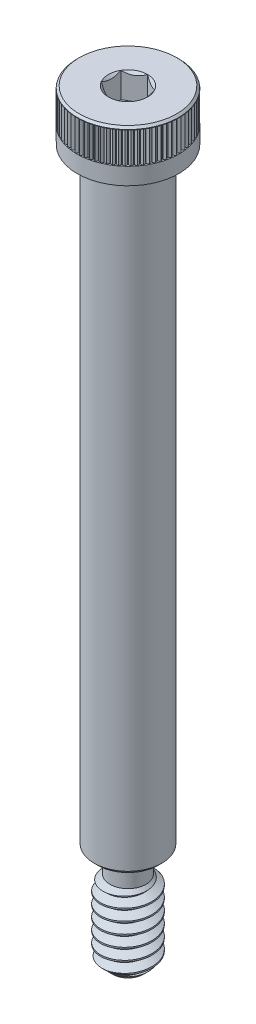
SolidWorks part; units mm, degrees
material "AISI 304"
ref_plane "Front" through (0, 0, 0) normal (0, 0, 1) x (1, 0, 0)
ref_plane "Top" through (0, 0, 0) normal (0, 1, 0) x (1, 0, 0)
ref_plane "Right" through (0, 0, 0) normal (1, 0, 0) x (0, 0, -1)
sketch "Sketch1" plane through (0, 0, 0) normal (0, 1, 0) x (1, 0, 0)
  circle A0 centre (0, 0) radius 4.7625
  point P3 (0, -4.7625)
  dimension "Head Dia" = 9.525
extrude "Extrude1" add sketch "Sketch1" along normal blind 4.7625
sketch "Sketch2" plane through (0, 4.7625, 0) normal (0, 1, 0) x (-1, 0, 0)
  line L1 (0, -1.8331) -> (1.5875, -0.9165)
  line L2 (1.5875, -0.9165) -> (1.5875, 0.9165)
  line L3 (1.5875, 0.9165) -> (0, 1.8331)
  line L4 (0, 1.8331) -> (-1.5875, 0.9165)
  line L5 (-1.5875, 0.9165) -> (-1.5875, -0.9165)
  line L6 (-1.5875, -0.9165) -> (0, -1.8331)
  circle A0 centre (0, 0) radius 1.5875 construction
  circle A1 centre (0, 0) radius 4.7625 construction
  dimension "Hex Key" = 3.175
extrude "Cut-Extrude1" cut sketch "Sketch2" against normal blind 2.3813
sketch "Sketch4" plane through (0, 0, 0) normal (0, -1, 0) x (1, 0, 0)
  circle A0 centre (0, 0) radius 3.175
  circle A1 centre (0, 0) radius 4.7625 construction
  dimension "Shoulder Dia" = 6.35
extrude "Extrude2" add sketch "Sketch4" along normal blind 57.15
sketch "Sketch5" plane through (0, -57.15, 0) normal (0, -1, 0) x (1, 0, 0)
  circle A0 centre (0, 0) radius 2.413
  circle A1 centre (0, 0) radius 3.175 construction
  dimension "Thread Dia" = 4.826
extrude "Extrude3" add sketch "Sketch5" along normal blind 9.525
chamfer "Chamfer1" distance 0.9525 angle 45 1 edges at (0, -66.675, -2.413)
sketch "Sketch12" plane through (0, -66.675, 0) normal (0, -1, 0) x (1, 0, 0)
  circle A0 centre (0, 0) radius 2.413
  circle A1 centre (0, 0) radius 2.413 construction
curve "Helix/Spiral1" pitch 1.0583 height 9.525 turns 9 parameters "Thread Pitch "=1.0583
sketch "Sketch13" plane through (0, 0, 0) normal (0, 0, 1) x (1, 0, 0)
  line L0 (2.413, -66.675) -> (2.413, -67.601)
  line L1 (2.413, -67.601) -> (1.7256, -67.2042)
  line L2 (1.7256, -67.2042) -> (1.7256, -67.0719)
  line L3 (1.7256, -67.0719) -> (2.413, -66.675)
  line L4 (2.413, -67.138) -> (1.7256, -67.138) construction
  line L5 (2.413, -65.7225) -> (2.413, -57.15) construction
  line L6 (2.0693, -66.8734) -> (2.0693, -67.4026) construction
  line L7 (-1.4605, -66.675) -> (1.4605, -66.675) construction
  dimension "D1" = 60
  dimension "D2" = 0.1323
  dimension "D3" = 0.5292
sweep "Cut-Sweep1" cut profiles "Sketch13" path "Helix/Spiral1"
sketch "Sketch18" plane through (0, 0, 0) normal (0, 0, 1) x (1, 0, 0)
  line L0 (2.413, -57.15) -> (1.6891, -57.15)
  line L1 (1.6891, -57.15) -> (1.6891, -59.2582)
  line L2 (1.6891, -59.2582) -> (2.413, -59.9821)
  line L3 (2.413, -59.9821) -> (2.413, -57.15)
  line L4 (-3.175, -57.15) -> (3.175, -57.15) construction
  line L5 (0, 0) -> (0, -10.8393) construction
  dimension "D1" = 45
  dimension "B" = 2.1082
  dimension "A" = 3.3782
revolve "Cut-Revolve1" cut sketch "Sketch18" angle 360 about axis through (0, -57.15, 0) along (0, 1, 0)
ref_plane "Plane1" through (0, 1.5875, 0) normal (0, 1, 0) x (-1, 0, 0)
sketch "Sketch10" plane through (0, 1.5875, 0) normal (0, 1, 0) x (-1, 0, 0)
  line L0 (0, 0) -> (-4.5683, 0) construction
  line L1 (0, 0) -> (-11.9081, -0.5199) construction
  line L2 (-4.758, -0.2077) -> (-4.8277, -0.2108)
  line L3 (-4.758, -0.2077) -> (-4.581, -0.0308)
  line L4 (0, 0) -> (-11.9081, 0.5199) construction
  line L5 (-4.581, 0.0308) -> (-4.758, 0.2077)
  line L6 (-4.8277, -0.2108) -> (-4.8277, 0.2108)
  line L7 (-4.8277, 0.2108) -> (-4.758, 0.2077)
  circle A0 centre (0, 0) radius 4.7625 construction
  arc A2 (-4.581, -0.0308) -> (-4.581, 0.0308) centre (-4.6118, 0) ccw
  point P3 (-4.7625, 0)
  dimension "D4" = 0.0435
  dimension "D1" = 90
  dimension "D2" = 5
  dimension "D3" = 0.0697
  dimension "D5" = 0.1942
extrude "Cut-Extrude3" cut sketch "Sketch10" along normal offset from surface (2.9419 mm away) 0.2331 up to face at (0, 4.7625, 0)
chamfer "Chamfer2" distance 0.1942 angle 45 1 edges at (0, 4.7625, 4.7625)
pattern_circular "CirPattern2" count 72 over 360 about axis through (0, 0, 0) along (0, 1, 0) of "Cut-Extrude3"
sketch "Sketch14" plane through (0, 4.7625, 0) normal (0, 1, 0) x (1, 0, 0)
  circle A0 centre (0, 0) radius 4.7625
  arc A1 (-1.4321, 4.5421) -> (-4.5421, -1.4321) centre (0, 0) ccw construction
sketch "Sketch15" plane through (0, 0, 0) normal (1, 0, 0) x (0, 0, -1)
  line L0 (-2.413, -57.15) -> (-2.413, -66.675)
  line L1 (2.413, -66.675) -> (2.413, -57.15)
  line L2 (-3.175, -57.15) -> (3.175, -57.15) construction
  point P7 (-2.413, -62.7062)
  point P9 (2.413, -62.7062)
  point P10 (-2.413, -59.2582)
  point P11 (2.413, -59.2582)
  dimension "D1" = 3.9688
sketch "Sketch16" plane through (0, 0, 0) normal (1, 0, 0) x (0, 0, -1)
  line L0 (-3.175, 0) -> (-3.175, -57.15)
  line L1 (3.175, 0) -> (3.175, -57.15)
  dimension "Shoulder Length" = 57.15
sketch "Sketch17" plane through (0, -57.15, 0) normal (0, -1, 0) x (1, 0, 0)
  circle A0 centre (0, 0) radius 3.175
  circle A1 centre (0, 0) radius 3.175 construction
  dimension "Shoulder Dia" = 6.35
fillet "Fillet1" radius 0.5292 1 edges at (0, -57.15, -1.6891)
chamfer "Chamfer3" distance 0.3528 angle 45 1 edges at (0, -57.15, -3.175)
sketch "Sketch19" plane through (0, 4.7625, 0) normal (0, 1, 0) x (1, 0, 0)
  circle A0 centre (0, 0) radius 1.8331
extrude "Extrude4" cut sketch "Sketch19" against normal through all draft 45
equation "\"D1@Cut-Extrude1\"=\"Head Ht@Extrude1\"/2"
equation "\"D1@Chamfer1\" = \"Thread Length@Extrude3\" * .1"
equation "\"D3@Helix/Spiral1\" = \"Thread Length@Extrude3\""
equation "\"D2@Sketch13\" = \"Thread Pitch @Helix/Spiral1\" * .125"
equation "\"D3@Sketch13\" = \"Thread Pitch @Helix/Spiral1\" * .5"
equation "\"D3@Sketch10\" = \"Head Dia@Sketch1\" * .0073205143"
equation "\"D4@Sketch10\" = \"Head Dia@Sketch1\" * .0045714286"
equation "\"Shoulder Length@Sketch16\" = \"Shoulder Length@Extrude2\""
equation "\"Shoulder Dia@Sketch17\" = \"Shoulder Dia@Sketch4\""
equation "\"D1@Plane1\" = \"Head Ht@Extrude1\"*2/3"
equation "\"D1@Chamfer2\" = \"D5@Sketch10\""
equation "\"D1@Cut-Extrude3\"=\"D5@Sketch10\"*1.2"
equation "\"D1@Fillet1\" = \"Thread Pitch @Helix/Spiral1\"*.50"
equation "\"D1@Chamfer3\" = \"Thread Pitch @Helix/Spiral1\"/3"
equation "\"D1@Sketch15\" = \"Thread Pitch @Helix/Spiral1\"*3.7500"
